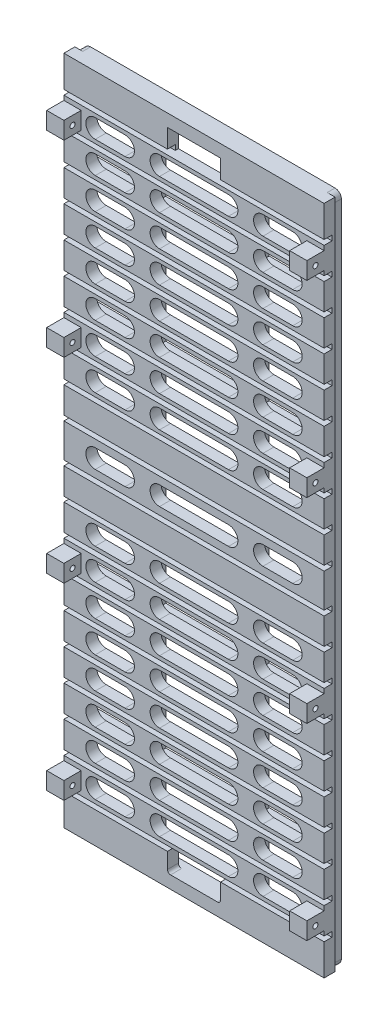
SolidWorks part; units mm, degrees
note: '?' marks a value the reader was unsure of.
material "6061-T6 (SS)"
ref_plane "Front Plane" through (0, 0, 0) normal (0, 0, 1) x (1, 0, 0)
ref_plane "Top Plane" through (0, 0, 0) normal (0, 1, 0) x (1, 0, 0)
ref_plane "Right Plane" through (0, 0, 0) normal (1, 0, 0) x (0, 0, -1)
sketch "Sketch1" plane through (0, 0, 0) normal (0, 0, 1) x (1, 0, 0)
  line L1 (-41.5, -107) -> (41.5, -107)
  line L2 (-41.5, -107) -> (-41.5, 107)
  line L3 (-41.5, 107) -> (41.5, 107)
  line L4 (41.5, -107) -> (41.5, 107)
  line L5 (-41.5, -107) -> (41.5, 107) construction
  line L6 (-41.5, 107) -> (41.5, -107) construction
  point P0 (0, 0)
  dimension "D1" = 83
  dimension "D2" = 214
extrude "Boss-Extrude1" add sketch "Sketch1" along normal blind 8.4
sketch "Sketch2" plane through (0, 107, 0) normal (0, 1, 0) x (1, 0, 0)
  line L0 (41.5, -8.4) -> (41.5, 0) construction
  line L1 (-41.5, -8.4) -> (35.5, -8.4)
  line L2 (-41.5, -8.4) -> (-41.5, -3.5)
  line L3 (-41.5, -3.5) -> (35.5, -3.5)
  line L4 (35.5, -8.4) -> (35.5, -3.5)
  dimension "D1" = 4.9
  dimension "D2" = 6
extrude "Cut-Extrude1" cut sketch "Sketch2" against normal through all
sketch "Sketch3" plane through (41.5, 0, 0) normal (1, 0, 0) x (0, 0, -1)
  line L0 (-8.4, -107) -> (-8.4, 107) construction
  line L1 (-8.4, 97) -> (-1, 97)
  line L2 (-8.4, 97) -> (-8.4, 95.4)
  line L3 (-8.4, 95.4) -> (-1, 95.4)
  line L4 (-1, 97) -> (-1, 95.4)
  line L5 (-8.4, 107) -> (0, 107) construction
  dimension "D1" = 1.6
  dimension "D2" = 7.4
  dimension "D3" = 10
extrude "Cut-Extrude2" cut sketch "Sketch3" against normal through all
pattern_linear "LPattern1" count 10 spacing 10 along (0, -1, 0) of "Cut-Extrude2"
mirror "Mirror8" about plane through (0, 0, 0) normal (0, 1, 0) of "LPattern1", "Cut-Extrude2"
sketch "Sketch22" plane through (0, 0, 3.5) normal (0, 0, 1) x (1, 0, 0)
  line L0 (-18, 118.4636) -> (-18, 62.547) construction
  line L1 (-31.5, 91.2) -> (-22, 91.2) construction
  line L2 (-31.5, 94.2) -> (-22, 94.2)
  line L3 (-31.5, 88.2) -> (-22, 88.2)
  line L5 (-15, 118.4636) -> (-15, 62.547) construction
  line L6 (15, 118.4636) -> (15, 62.547) construction
  line L7 (18, 118.4636) -> (18, 62.547) construction
  line L8 (0, 95.4) -> (0, 87) construction
  line L9 (-41.5, 95.4) -> (41.5, 95.4) construction
  line L10 (-41.5, 87) -> (41.5, 87) construction
  line L11 (31.5, 91.2) -> (22, 91.2) construction
  line L12 (31.5, 94.2) -> (22, 94.2)
  line L13 (31.5, 88.2) -> (22, 88.2)
  line L14 (-11, 91.2) -> (11, 91.2) construction
  line L15 (-11, 94.2) -> (11, 94.2)
  line L16 (-11, 88.2) -> (11, 88.2)
  line L17 (-14, 91.2) -> (-15, 91.2) construction
  line L18 (-19, 91.2) -> (-18, 91.2) construction
  line L19 (35.5, 87) -> (35.5, 95.4) construction
  arc A0 (-31.5, 94.2) -> (-31.5, 88.2) centre (-31.5, 91.2) ccw
  arc A1 (-22, 88.2) -> (-22, 94.2) centre (-22, 91.2) ccw
  arc A2 (31.5, 94.2) -> (31.5, 88.2) centre (31.5, 91.2) cw
  arc A3 (22, 88.2) -> (22, 94.2) centre (22, 91.2) cw
  arc A4 (-11, 94.2) -> (-11, 88.2) centre (-11, 91.2) ccw
  arc A5 (11, 88.2) -> (11, 94.2) centre (11, 91.2) ccw
  point P2 (-26.75, 91.2)
  point P7 (34.5, 91.2)
  point P20 (26.75, 91.2)
  point P26 (0, 91.2)
  point P28 (0, 91.2)
  point P45 (-19, 91.2)
  dimension "D1" = 3
  dimension "D2" = 1
  dimension "D3" = 1
  dimension "D4" = 3
  dimension "D5" = 30
extrude "Cut-Extrude6" cut sketch "Sketch22" against normal through all
pattern_linear "LPattern3" count 8 spacing 10 along (0, -1, 0) of "Cut-Extrude6"
mirror "Mirror1" about plane through (0, 0, 0) normal (0, 1, 0) of "LPattern3", "Cut-Extrude6"
sketch "Sketch23" plane through (0, 0, 3.5) normal (0, 0, 1) x (1, 0, 0)
  line L4 (-37.4238, 5.4) -> (-37.4238, -5.4) construction
  line L6 (35.5, 5.4) -> (-41.5, 5.4) construction
  line L8 (35.5, -5.4) -> (-41.5, -5.4) construction
  line L9 (31.5, 94.2) -> (22, 94.2) construction
  line L10 (22, 88.2) -> (31.5, 88.2) construction
  line L11 (11, 94.2) -> (-11, 94.2) construction
  line L12 (-11, 88.2) -> (11, 88.2) construction
  line L13 (-22, 94.2) -> (-31.5, 94.2) construction
  line L14 (-31.5, 88.2) -> (-22, 88.2) construction
  line L15 (31.5, 94.2) -> (22, 94.2) construction
  line L16 (22, 88.2) -> (31.5, 88.2) construction
  line L17 (11, 94.2) -> (-11, 94.2) construction
  line L18 (-11, 88.2) -> (11, 88.2) construction
  line L19 (-22, 94.2) -> (-31.5, 94.2) construction
  line L20 (-31.5, 88.2) -> (-22, 88.2) construction
  line L21 (31.5, 3) -> (22, 3)
  line L24 (22, -3) -> (31.5, -3)
  line L25 (11, 3) -> (-11, 3)
  line L26 (-11, -3) -> (11, -3)
  line L27 (-22, 3) -> (-31.5, 3)
  line L28 (-31.5, -3) -> (-22, -3)
  line L29 (-34.5, 0) -> (-37.4238, 0) construction
  arc A6 (22, 94.2) -> (22, 88.2) centre (22, 91.2) ccw construction
  arc A7 (31.5, 88.2) -> (31.5, 94.2) centre (31.5, 91.2) ccw construction
  arc A8 (-11, 94.2) -> (-11, 88.2) centre (-11, 91.2) ccw construction
  arc A9 (11, 88.2) -> (11, 94.2) centre (11, 91.2) ccw construction
  arc A10 (-31.5, 94.2) -> (-31.5, 88.2) centre (-31.5, 91.2) ccw construction
  arc A11 (-22, 88.2) -> (-22, 94.2) centre (-22, 91.2) ccw construction
  arc A12 (22, 94.2) -> (22, 88.2) centre (22, 91.2) ccw construction
  arc A13 (31.5, 88.2) -> (31.5, 94.2) centre (31.5, 91.2) ccw construction
  arc A14 (-11, 94.2) -> (-11, 88.2) centre (-11, 91.2) ccw construction
  arc A15 (11, 88.2) -> (11, 94.2) centre (11, 91.2) ccw construction
  arc A16 (-31.5, 94.2) -> (-31.5, 88.2) centre (-31.5, 91.2) ccw construction
  arc A17 (-22, 88.2) -> (-22, 94.2) centre (-22, 91.2) ccw construction
  arc A18 (22, 3) -> (22, -3) centre (22, 0) ccw
  arc A19 (31.5, -3) -> (31.5, 3) centre (31.5, 0) ccw
  arc A20 (-11, 3) -> (-11, -3) centre (-11, 0) ccw
  arc A21 (11, -3) -> (11, 3) centre (11, 0) ccw
  arc A22 (-31.5, 3) -> (-31.5, -3) centre (-31.5, 0) ccw
  arc A23 (-22, -3) -> (-22, 3) centre (-22, 0) ccw
  dimension "D1" = 2
extrude "Cut-Extrude7" cut sketch "Sketch23" against normal through all
sketch "Sketch4" plane through (0, 0, 0) normal (0, 0, -1) x (-1, 0, 0)
  line L0 (-41.5, 107) -> (41.5, 107) construction
  line L1 (-39, 107) -> (39, 107)
  line L2 (-41, 105) -> (-41, -105)
  line L3 (-39, -107) -> (39, -107)
  line L4 (41, 105) -> (41, -105)
  line L5 (-35, -103) -> (35, -103)
  line L6 (-37, -101) -> (-37, 101)
  line L7 (-35, 103) -> (35, 103)
  line L8 (37, -101) -> (37, 101)
  line L9 (-37, -103) -> (37, 103) construction
  line L10 (-37, 103) -> (37, -103) construction
  line L11 (41.5, -107) -> (-41.5, -107) construction
  arc A0 (-41, -105) -> (-39, -107) centre (-39, -105) ccw
  arc A1 (39, -107) -> (41, -105) centre (39, -105) ccw
  arc A2 (39, 107) -> (41, 105) centre (39, 105) cw
  arc A3 (-39, 107) -> (-41, 105) centre (-39, 105) ccw
  arc A4 (35, -103) -> (37, -101) centre (35, -101) ccw
  arc A5 (-35, -103) -> (-37, -101) centre (-35, -101) cw
  arc A6 (-37, 101) -> (-35, 103) centre (-35, 101) cw
  arc A7 (35, 103) -> (37, 101) centre (35, 101) cw
  point P10 (41.5, -107)
  point P15 (-41.5, 107)
  point P16 (0, 0)
  dimension "D1" = 2
  dimension "D4" = 2
  dimension "D2" = 4
  dimension "D3" = 4
  dimension "D5" = 41
  dimension "D6" = 41
extrude "solarBezel" add sketch "Sketch4" along normal blind 2.5
hole_wizard "M2x0.4 Tapped Hole2" positions "Sketch10" profile "Sketch11" tap size "M2x0.4" standard "ANSI Metric"
sketch "Sketch10" plane through (0, 0, -2.5) normal (0, 0, -1) x (-1, 0, 0)
  line L0 (39, 107) -> (-39, 107) construction
  line L3 (-37, 0) -> (37, 0) construction
  line L4 (-37, 101) -> (-37, -101) construction
  line L5 (37, -101) -> (37, 101) construction
  line L6 (-39, 102) -> (39, 102) construction
  line L8 (35, 103) -> (-35, 103) construction
  line L9 (-41, 102) -> (-37, 102) construction
  line L10 (-41, 105) -> (-41, -105) construction
  point P0 (-39, 102)
  point P15 (39, 102)
  point P16 (39, 72)
  point P17 (39, 42)
  point P18 (39, 12)
  point P20 (-39, 72)
  point P21 (-39, 42)
  point P22 (-39, 12)
  point P32 (39, -102)
  point P34 (-39, -12)
  point P35 (-39, -42)
  point P36 (-39, -72)
  point P38 (39, -12)
  point P39 (39, -42)
  point P40 (39, -72)
  point P41 (-39, -102)
  point P49 (0, 102)
  point P52 (0, 103)
  point P62 (-39, 102)
  dimension "D1" = 5
  dimension "D4" = 30
  dimension "D5" = 2
  dimension "D3" = 4
sketch "Sketch11" plane through (39, 102, -2.5) normal (1, 0, 0) x (0, 1, 0)
  line L0 (0, 0) -> (0, 5.6807)
  line L1 (0, 5.6807) -> (0.8, 5.2)
  line L2 (0.8, 5.2) -> (0.8, 0)
  line L5 (0.8, 0) -> (0, 0)
  line L10 (0, 5.6807) -> (-0.8, 5.2) construction
  line L11 (0, -6.35) -> (0, 107.95) construction
  dimension "Tap Drill Dia." = 1.6
  dimension "Tap Drill Depth" = 5.2
  dimension "Drill Angle" = 118
cosmetic thread "Hole Thread12" parameters "D1"=4, "D2"=2
cosmetic thread "Hole Thread13" parameters "D1"=4, "D2"=2
cosmetic thread "Hole Thread14" parameters "D1"=4, "D2"=2
cosmetic thread "Hole Thread15" parameters "D1"=4, "D2"=2
cosmetic thread "Hole Thread17" parameters "D1"=4, "D2"=2
cosmetic thread "Hole Thread18" parameters "D1"=4, "D2"=2
cosmetic thread "Hole Thread19" parameters "D1"=4, "D2"=2
cosmetic thread "Hole Thread21" parameters "D1"=4, "D2"=2
cosmetic thread "Hole Thread23" parameters "D1"=4, "D2"=2
cosmetic thread "Hole Thread24" parameters "D1"=4, "D2"=2
cosmetic thread "Hole Thread25" parameters "D1"=4, "D2"=2
cosmetic thread "Hole Thread27" parameters "D1"=4, "D2"=2
cosmetic thread "Hole Thread28" parameters "D1"=4, "D2"=2
cosmetic thread "Hole Thread29" parameters "D1"=4, "D2"=2
cosmetic thread "Hole Thread30" parameters "D1"=4, "D2"=2
cosmetic thread "Hole Thread31" parameters "D1"=4, "D2"=2
sketch "Sketch25" plane through (0, 0, -2.5) normal (0, 0, -1) x (-1, 0, 0)
  line L0 (-37, 0) -> (37, 0) construction
  line L1 (-37, 77.7) -> (37, 77.7)
  line L2 (-37, 77.7) -> (-37, 74.7)
  line L3 (-37, 74.7) -> (37, 74.7)
  line L4 (37, 77.7) -> (37, 74.7)
  line L5 (-37, 37.7) -> (37, 37.7)
  line L6 (-37, 37.7) -> (-37, 34.7)
  line L7 (-37, 34.7) -> (37, 34.7)
  line L8 (37, 37.7) -> (37, 34.7)
  line L9 (-37, 10) -> (37, 10)
  line L10 (-37, 10) -> (-37, 7)
  line L11 (-37, 7) -> (37, 7)
  line L12 (37, 10) -> (37, 7)
  line L13 (-41.5, 75.4) -> (-41.5, 77) construction
  line L14 (-37, 101) -> (-37, -101) construction
  line L15 (37, -101) -> (37, 101) construction
  line L16 (-41.5, 35.4) -> (-41.5, 37) construction
  line L18 (-37, 101) -> (-37, -101) construction
  line L19 (37, -101) -> (37, 101) construction
  line L20 (-37, -77.7) -> (-37, -74.7)
  line L21 (-37, -74.7) -> (37, -74.7)
  line L22 (37, -77.7) -> (37, -74.7)
  line L23 (-37, -77.7) -> (37, -77.7)
  line L24 (-37, -37.7) -> (-37, -34.7)
  line L25 (-37, -37.7) -> (37, -37.7)
  line L26 (37, -37.7) -> (37, -34.7)
  line L27 (-37, -34.7) -> (37, -34.7)
  line L28 (-37, -10) -> (-37, -7)
  line L29 (-37, -10) -> (37, -10)
  line L30 (37, -10) -> (37, -7)
  line L31 (-37, -7) -> (37, -7)
  line L32 (39, 107) -> (-39, 107) construction
  point P14 (-37, 76.2)
  point P17 (-41.5, 76.2)
  point P20 (-37, 36.2)
  point P23 (-41.5, 36.2)
  dimension "D1" = 3
  dimension "D2" = 100
extrude "Boss-Extrude4" add sketch "Sketch25" against normal up to surface (2.5 mm away) up to face at (0, 0, 0)
sketch "Sketch26" plane through (0, 0, -2.5) normal (0, 0, -1) x (-1, 0, 0)
  line L0 (0, 103) -> (0, -103) construction
  line L1 (-18, 103) -> (-15, 103)
  line L2 (-18, 103) -> (-18, -103)
  line L3 (-18, -103) -> (-15, -103)
  line L4 (-15, 103) -> (-15, -103)
  line L5 (35, 103) -> (-35, 103) construction
  line L6 (-35, -103) -> (35, -103) construction
  line L7 (35, 103) -> (-35, 103) construction
  line L8 (-35, -103) -> (35, -103) construction
  line L9 (18, 103) -> (15, 103)
  line L10 (18, 103) -> (18, -103)
  line L11 (18, -103) -> (15, -103)
  line L12 (15, 103) -> (15, -103)
  dimension "D1" = 3
  dimension "D2" = 30
extrude "Boss-Extrude5" add sketch "Sketch26" against normal up to surface (2.5 mm away) up to face at (0, 94.0381, 0)
fillet "Fillet2" [suppressed] radius 3
hole_wizard "M2x0.4 Tapped Hole6" [suppressed] positions "Sketch28" profile "Sketch29" tap size "M2x0.4" standard "ANSI Metric"
sketch "Sketch28" plane through (0, 0, -2.5) normal (0, 0, -1) x (-1, 0, 0)
  line L0 (24.3618, 107) -> (24.3618, 103) construction
  line L1 (39, 107) -> (-39, 107) construction
  line L2 (35, 103) -> (21, 103) construction
  line L4 (15, 64.1165) -> (18, 64.1165) construction
  line L5 (15, 71.7) -> (15, 40.7) construction
  line L6 (18, 40.7) -> (18, 71.7) construction
  line L8 (24.3618, 10) -> (24.3618, 7) construction
  line L9 (34, 10) -> (21, 10) construction
  line L10 (21, 7) -> (34, 7) construction
  line L12 (0, 107) -> (0, -107) construction
  line L13 (-39, -107) -> (39, -107) construction
  line L15 (-41, 0) -> (41, 0) construction
  line L16 (-41, 105) -> (-41, -105) construction
  line L17 (41, -105) -> (41, 105) construction
  point P0 (16.5, 105)
  point P2 (16.5, 8.5)
  point P13 (24.3618, 105)
  point P21 (16.5, 64.1165)
  point P31 (24.3618, 8.5)
  point P48 (-16.5, 8.5)
  point P49 (-16.5, 105)
  point P50 (16.5, -8.5)
  point P51 (16.5, -105)
  point P52 (-16.5, -105)
  point P53 (-16.5, -8.5)
sketch "Sketch29" plane through (-16.5, 105, -2.5) normal (1, 0, 0) x (0, 1, 0)
  line L0 (0, 0) -> (0, 10.9)
  line L1 (0, 10.9) -> (0.8, 10.9)
  line L2 (0.8, 10.9) -> (0.8, 0)
  line L5 (0.8, 0) -> (0, 0)
  line L11 (0, -6.35) -> (0, 107.95) construction
  dimension "Thru Tap Drill Dia." = 1.6
  dimension "Thru Tap Drill Depth" = 10.9
cosmetic thread "Hole Thread35" [suppressed] parameters "D2"=2
cosmetic thread "Hole Thread36" [suppressed] parameters "D2"=2
cosmetic thread "Hole Thread37" [suppressed] parameters "D2"=2
cosmetic thread "Hole Thread38" [suppressed] parameters "D2"=2
cosmetic thread "Hole Thread39" [suppressed] parameters "D2"=2
cosmetic thread "Hole Thread40" [suppressed] parameters "D2"=2
cosmetic thread "Hole Thread41" [suppressed] parameters "D2"=2
cosmetic thread "Hole Thread42" [suppressed] parameters "D2"=2
sketch "Sketch19" plane through (0, -107, 0) normal (0, -1, 0) x (1, 0, 0)
  line L1 (35.5, 9.3479) -> (45.967, 9.3479)
  line L2 (35.5, 9.3479) -> (35.5, 3.5)
  line L3 (35.5, 3.5) -> (45.967, 3.5)
  line L4 (45.967, 9.3479) -> (45.967, 3.5)
extrude "removeOldPillars" cut sketch "Sketch19" against normal through all
sketch "Sketch5" plane through (0, 0, 3.5) normal (0, 0, 1) x (1, 0, 0)
  line L0 (41.5, 107) -> (-41.5, 107) construction
  line L1 (-36, 88.45) -> (-41.5, 88.45)
  line L2 (-36, 88.45) -> (-36, 93.95)
  line L3 (-36, 93.95) -> (-41.5, 93.95)
  line L4 (-41.5, 88.45) -> (-41.5, 93.95)
  line L5 (-36, 88.45) -> (-41.5, 93.95) construction
  line L6 (-36, 93.95) -> (-41.5, 88.45) construction
  line L9 (-41.5, 87) -> (-41.5, 95.4) construction
  point P0 (-38.75, 91.2)
  dimension "D1" = 5.5
  dimension "D2" = 5.5
  dimension "D3" = 13.05
extrude "Boss-Extrude3" add sketch "Sketch5" along normal blind 5.5
hole_wizard "M2x0.4 Tapped Hole5" positions "Sketch20" profile "Sketch21" tap size "M2x0.4" standard "ANSI Metric" end condition through all
sketch "Sketch20" plane through (-41.5, 0, 0) normal (-1, 0, 0) x (0, 0, 1)
  line L0 (9, 93.95) -> (3.5, 88.45) construction
  point P0 (6.25, 91.2)
  point P10 (6.25, 91.2)
cosmetic thread "Hole Thread33" parameters "D2"=2
sketch "Sketch21" plane through (-41.5, 91.2, 6.25) normal (0, 1, 0) x (0, 0, 1)
  line L0 (0, 0) -> (0, 83)
  line L1 (0, 83) -> (0.8, 83)
  line L2 (0.8, 83) -> (0.8, 0)
  line L5 (0.8, 0) -> (0, 0)
  line L11 (0, -6.35) -> (0, 107.95) construction
  dimension "Thru Tap Drill Dia." = 1.6
  dimension "Thru Tap Drill Depth" = 83
pattern_linear "LPattern2" count 2 spacing 60 along (0, -1, 0) of "Boss-Extrude3", "M2x0.4 Tapped Hole5"
mirror "Mirror2" about plane through (0, 0, 0) normal (0, 1, 0) of "LPattern2", "Boss-Extrude3", "M2x0.4 Tapped Hole5"
mirror "Mirror6" about plane through (0, 0, 0) normal (1, 0, 0) of "Boss-Extrude3", "LPattern2", "Mirror2", "M2x0.4 Tapped Hole5"
sketch "Sketch6" plane through (0, 0, 0) normal (0, 0, -1) x (-1, 0, 0)
  line L0 (35, 103) -> (18, 103) construction
  line L1 (-7.475, 95.4) -> (7.475, 95.4)
  line L2 (-8.475, 96.4) -> (-8.475, 102)
  line L3 (-7.475, 103) -> (7.475, 103)
  line L4 (8.475, 96.4) -> (8.475, 102)
  line L5 (-8.475, 95.4) -> (8.475, 103) construction
  line L6 (-8.475, 103) -> (8.475, 95.4) construction
  line L10 (41.5, 95.4) -> (-41.5, 95.4) construction
  arc A0 (-8.475, 102) -> (-7.475, 103) centre (-7.475, 102) cw
  arc A1 (7.475, 103) -> (8.475, 102) centre (7.475, 102) cw
  arc A2 (7.475, 95.4) -> (8.475, 96.4) centre (7.475, 96.4) ccw
  arc A3 (-7.475, 95.4) -> (-8.475, 96.4) centre (-7.475, 96.4) cw
  point P0 (0, 99.2)
  dimension "D3" = 1
  dimension "D2" = 16.95
extrude "Cut-Extrude3" cut sketch "Sketch6" against normal through all
mirror "Mirror3" about plane through (0, 0, 0) normal (0, 1, 0) of "Cut-Extrude3"
fillet "Fillet1" [suppressed] radius 2
hole_wizard "M2x0.4 Tapped Hole3" [suppressed] positions "Sketch13" profile "Sketch14" tap size "M2x0.4" standard "ANSI Metric"
sketch "Sketch13" [suppressed] plane through (0, -107, 0) normal (0, -1, 0) x (-1, 0, 0)
  line L0 (-41.5, -3.5) -> (41.5, -3.5) construction
  line L5 (0, 2.5) -> (0, -3.5) construction
  line L6 (-39, 2.5) -> (39, 2.5) construction
  line L7 (-41.5, -3.5) -> (41.5, -3.5) construction
  point P0 (-27.5, 0)
  point P42 (27.5, 0)
  dimension "D1" = 3.5
  dimension "D2" = 55
sketch "Sketch14" [suppressed] plane through (27.5, -107, 0) normal (1, 0, 0) x (0, 0, -1)
  line L0 (0, 0) -> (0, 3.4807)
  line L1 (0, 3.4807) -> (0.8, 3)
  line L2 (0.8, 3) -> (0.8, 0)
  line L5 (0.8, 0) -> (0, 0)
  line L10 (0, 3.4807) -> (-0.8, 3) construction
  line L11 (0, -6.35) -> (0, 107.95) construction
  dimension "Tap Drill Dia." = 1.6
  dimension "Tap Drill Depth" = 3
  dimension "Drill Angle" = 118
cosmetic thread "Hole Thread34" [suppressed] parameters "D1"=3, "D2"=2
cosmetic thread "Hole Thread43" [suppressed] parameters "D1"=3, "D2"=2
mirror "Mirror9" [suppressed] about plane through (0, 0, 0) normal (0, 1, 0)
sketch "Sketch15" [suppressed] plane through (0, 0, 0) normal (0, 0, -1) x (-1, 0, 0)
  line L2 (-41.5, 5.4) -> (41.5, 5.4) construction
  line L3 (-41.5, 5.4) -> (41.5, 5.4) construction
  line L4 (0, 5.4) -> (0, -5.4) construction
  line L5 (-37, 54.7) -> (37, 54.7) construction
  line L6 (41.5, 7) -> (-41.5, 7) construction
  line L7 (37, -101) -> (37, -80.7) construction
  line L8 (-37, 101) -> (-37, 80.7) construction
  line L9 (41.5, 7) -> (-41.5, 7) construction
  line L12 (-22.0168, 0) -> (22.0168, 0) construction
  line L13 (-37, -54.7) -> (37, -54.7) construction
  line L15 (-31.5, 54.2) -> (-22, 54.2) construction
  text T0 "v0.8.1 -- 2018-01-21" font "Century Gothic" height 5
  point P10 (0, 0)
  point P13 (0, 0)
  dimension "D1" = 0.5
extrude "VERSION_LABEL" [suppressed] cut sketch "Sketch15" against normal blind 0.3 draft 45
sketch "Sketch24" [suppressed] plane through (0, 0, 0) normal (0, 0, -1) x (-1, 0, 0)
  line L0 (15.5, 34.7) -> (35, 34.7) construction
  line L4 (22, 34.2) -> (31.5, 34.2) construction
  line L5 (37, -101) -> (37, -80.7) construction
  text T0 "±Y" font "Century Gothic" height 5
  dimension "D1" = 0.5
  dimension "D2" = 2
extrude "axisLabel" [suppressed] cut sketch "Sketch24" against normal blind 10 draft 45
sketch "Sketch27" [suppressed] plane through (0, 0, 3.5) normal (0, 0, 1) x (1, 0, 0)
  line L0 (-41.5, 98) -> (-8.475, 98) construction
  line L1 (-41.5, 97) -> (-41.5, 107) construction
  line L3 (-41.5, 97) -> (-10.475, 97) construction
  line L4 (-8.475, 99) -> (-8.475, 102) construction
  line L5 (8.475, 98) -> (41.5, 98) construction
  line L6 (41.5, 107) -> (41.5, 97) construction
  line L7 (8.475, 102) -> (8.475, 99) construction
  text T0 "v0.8.3" font "Century Gothic" height 5
  text T1 "'18-02-04" font "Century Gothic" height 5
  dimension "D1" = 1
extrude "cantonLabel" [suppressed] cut sketch "Sketch27" against normal blind 0.3 draft 45
ref_axis "Axis1" [suppressed] through (0, 0, -3.159) along (0, 0, 1)?
pattern_circular "CirPattern1" [suppressed] count 2 over 360 about axis through (0, 0, -3.159) along (0, 0, 1)
sketch "Sketch30" plane through (0, 0, 0) normal (0, 0, -1) x (-1, 0, 0)
  line L0 (-8.475, 102) -> (-8.475, 96.4) construction
  line L1 (-8.475, 103) -> (8.475, 103)
  line L2 (-8.475, 103) -> (-8.475, 95.4)
  line L3 (-8.475, 95.4) -> (8.475, 95.4)
  line L4 (8.475, 103) -> (8.475, 95.4)
  line L5 (8.475, 96.4) -> (8.475, 102) construction
  line L6 (7.475, 103) -> (-7.475, 103) construction
  line L7 (-7.475, 95.4) -> (7.475, 95.4) construction
extrude "Cut-Extrude8" cut sketch "Sketch30" against normal blind 10
